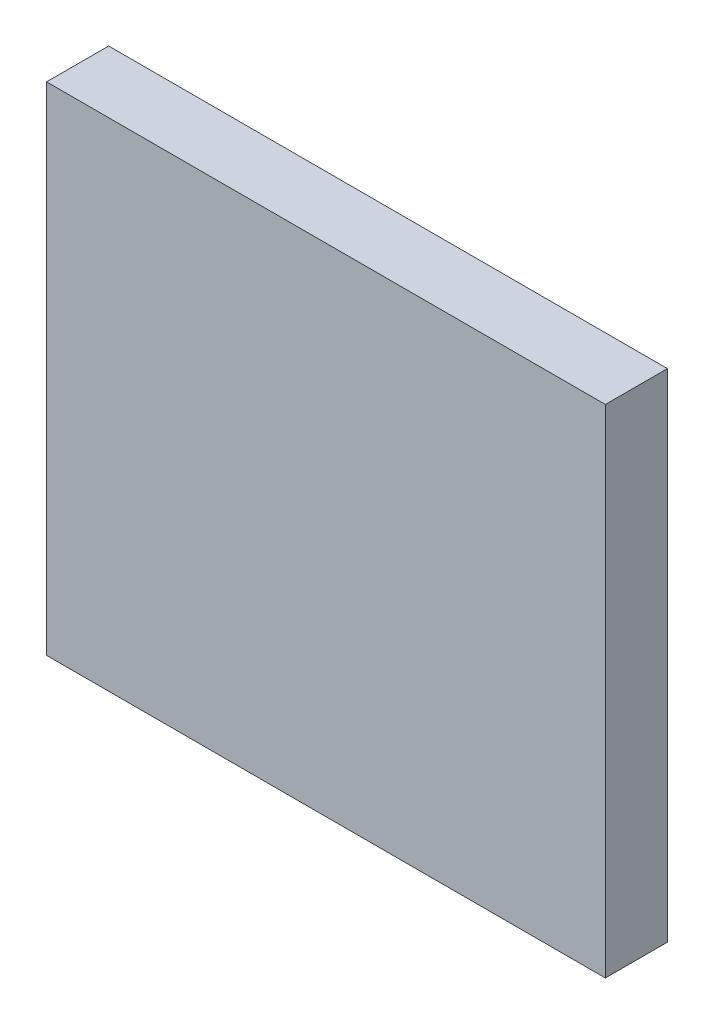
SolidWorks part; units mm, degrees
ref_plane "Plan de face" through (0, 0, 0) normal (0, 0, 1) x (1, 0, 0)
ref_plane "Plan de dessus" through (0, 0, 0) normal (0, 1, 0) x (1, 0, 0)
ref_plane "Plan de droite" through (0, 0, 0) normal (1, 0, 0) x (0, 0, -1)
sketch "Esquisse1" plane through (0, 0, 0) normal (0, 0, 1) x (1, 0, 0)
  line L1 (-135, -120) -> (135, -120)
  line L2 (-135, -120) -> (-135, 120)
  line L3 (-135, 120) -> (135, 120)
  line L4 (135, -120) -> (135, 120)
  line L5 (-135, -120) -> (135, 120) construction
  line L6 (-135, 120) -> (135, -120) construction
  point P1 (0, 0)
extrude "Boss.-Extru.1" add sketch "Esquisse1" along normal blind 30
